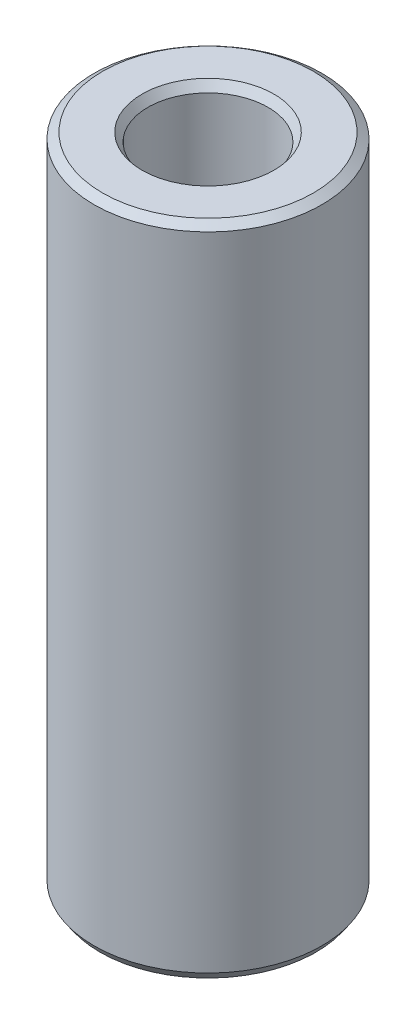
SolidWorks part; units mm, degrees
ref_plane "Front Plane" through (0, 0, 0) normal (0, 0, 1) x (1, 0, 0)
ref_plane "Top Plane" through (0, 0, 0) normal (0, 1, 0) x (1, 0, 0)
ref_plane "Right Plane" through (0, 0, 0) normal (1, 0, 0) x (0, 0, -1)
sketch "Sketch1" plane through (0, 0, 0) normal (0, 1, 0) x (1, 0, 0)
  circle A0 centre (0, 0) radius 40
  dimension "SLEEVE_OD" = 80
extrude "Boss-Extrude1" add sketch "Sketch1" along normal blind 230.4661
sketch "Sketch2" plane through (0, 0, 0) normal (0, 1, 0) x (1, 0, 0)
  circle A0 centre (0, 0) radius 21.1047
  dimension "BORE_D" = 42.2093
extrude "Cut-Extrude1" cut sketch "Sketch2" along normal through all
chamfer "Chamfer1" distance 2.0708 angle 55.209 4 edges at (0, 230.4661, 21.1047) (0, 0, 21.1047) (0, 0, 40) (0, 230.4661, 40) first distance on face at (0, 230.4661, 21.1047) first distance on face at (0, 0, 21.1047) first distance on face at (0, 230.4661, 40)
